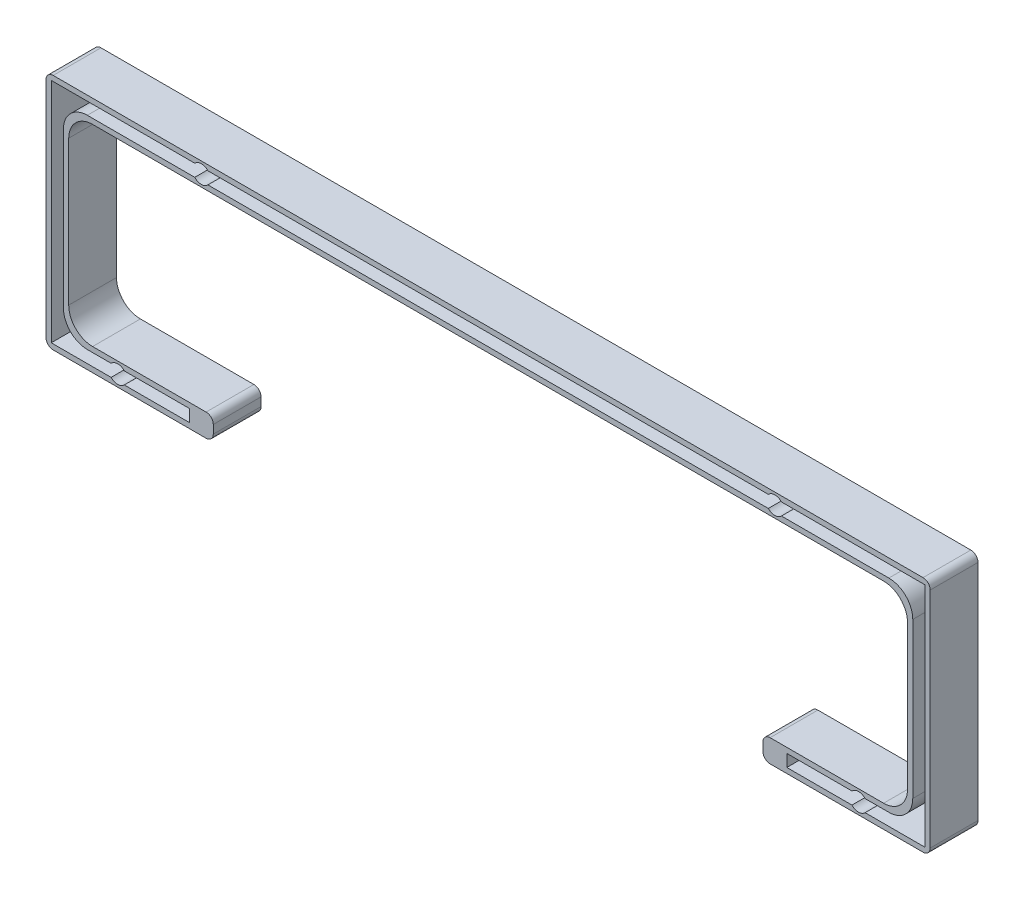
SolidWorks part; units mm, degrees
ref_plane "Front Plane" through (0, 0, 0) normal (0, 0, 1) x (1, 0, 0)
ref_plane "Top Plane" through (0, 0, 0) normal (0, 1, 0) x (1, 0, 0)
ref_plane "Right Plane" through (0, 0, 0) normal (1, 0, 0) x (0, 0, -1)
sketch "Sketch1" plane through (0, 0, 0) normal (0, 0, 1) x (1, 0, 0)
  line L0 (-115, 0) -> (-175.5, 0)
  line L1 (-175.5, 0) -> (-175.5, 80.5)
  line L2 (-175.5, 80.5) -> (175.5, 80.5)
  line L3 (0, 0) -> (0, 55.9082) construction
  line L4 (115, 0) -> (175.5, 0)
  line L5 (175.5, 0) -> (175.5, 80.5)
  line L6 (-115, -9.5) -> (-185, -9.5)
  line L7 (-185, -9.5) -> (-185, 90)
  line L8 (-185, 90) -> (185, 90)
  line L9 (185, -9.5) -> (185, 90)
  line L10 (115, -9.5) -> (185, -9.5)
  line L11 (-115, -9.5) -> (-115, 0)
  line L12 (115, -9.5) -> (115, 0)
  point P10 (0, 80.5)
  dimension "D1" = 9.5
  dimension "D2" = 90
  dimension "D3" = 70
  dimension "D4" = 370
extrude "Boss-Extrude1" add sketch "Sketch1" along normal blind 20
sketch "Sketch2" plane through (0, 0, 20) normal (0, 0, 1) x (1, 0, 0)
  line L1 (-125, -4.75) -> (-180.25, -4.75)
  line L2 (-180.25, -4.75) -> (-180.25, 85.25)
  line L3 (-180.25, 85.25) -> (180.25, 85.25)
  line L4 (180.25, 85.25) -> (180.25, -4.75)
  line L5 (180.25, -4.75) -> (125, -4.75)
  line L8 (-185, 90) -> (-185, -9.5) construction
  line L9 (-175.5, 0) -> (-175.5, 80.5) construction
  line L10 (-115, 0) -> (-175.5, 0) construction
  line L11 (185, 90) -> (-185, 90) construction
  line L12 (185, -9.5) -> (185, 90) construction
  line L13 (115, -9.5) -> (185, -9.5) construction
  line L14 (-115, -9.5) -> (-115, 0) construction
  line L15 (115, 0) -> (115, -9.5) construction
  dimension "D1" = 9.5
  dimension "D2" = 4.75
  dimension "D3" = 4.75
  dimension "D4" = 4.75
  dimension "D5" = 4.75
  dimension "D6" = 4.75
  dimension "D7" = 10
  dimension "D8" = 10
extrude "Cut-Extrude-Thin1" cut sketch "Sketch2" against normal offset from surface (17 mm away) 3 thin up to face at (0, 25.25, 0) thin type mid plane wall 5.1
fillet "Fillet1" radius 10 8 edges at (-175.5, 80.5, 10) (-175.5, 0, 10) (175.5, 0, 10) (175.5, 80.5, 10) (177.7, -2.2, 11.5) (177.7, 82.7, 11.5) (-177.7, -2.2, 11.5) (-177.7, 82.7, 11.5)
sketch "Sketch3" plane through (0, 0, 20) normal (0, 0, 1) x (1, 0, 0)
  line L0 (0, 0) -> (0, 23.1541) construction
  line L1 (185, 90) -> (-185, 90) construction
  line L2 (-165.5, 80.5) -> (165.5, 80.5) construction
  line L3 (-115, 0) -> (-165.5, 0) construction
  circle A0 centre (-120, 85.25) radius 3.75
  circle A1 centre (-120, 85.25) radius 2.25
  circle A2 centre (120, 85.25) radius 3.75
  circle A3 centre (120, 85.25) radius 2.25
  circle A4 centre (-155, -4.75) radius 3.75
  circle A5 centre (-155, -4.75) radius 2.25
  circle A6 centre (155, -4.75) radius 3.75
  circle A7 centre (155, -4.75) radius 2.25
  point P19 (0, 0)
  point P22 (-157.054, -4.75)
  dimension "D5" = 4.75
  dimension "D6" = 4.75
  dimension "D1" = 7.5
  dimension "D2" = 4.5
  dimension "D3" = 120
  dimension "D4" = 9.5
  dimension "D7" = 155
extrude "Cut-Extrude1" cut sketch "Sketch3" against normal up to surface (17 mm away) up to face at (0, 29, 3)
extrude "Cut-Extrude2" cut sketch "Sketch3<2>" against normal through all contours A1 | A5 | A7 | A3 region at (-120, 85.25, 20) region at (120, 85.25, 20) region at (-155, -4.75, 20) region at (155, -4.75, 20)
sketch "Sketch3<2>" plane through (0, 0, 20) normal (0, 0, 1) x (1, 0, 0) same geometry as "Sketch3"
fillet "Fillet2" radius 3 8 edges at (-115, -9.5, 10) (185, 90, 10) (115, -9.5, 10) (115, 0, 10) (-115, 0, 10) (185, -9.5, 10) (-185, -9.5, 10) (-185, 90, 10)
sketch "Sketch4" plane through (0, 0, 3) normal (0, 0, 1) x (1, 0, 0)
  line L0 (-152.2505, -2.2) -> (-125, -2.2) construction
  line L1 (-130, -2.2) -> (-125, -2.2)
  line L2 (-130, -2.2) -> (-130, -7.3)
  line L3 (-130, -7.3) -> (-125, -7.3)
  line L4 (-125, -2.2) -> (-125, -7.3)
  line L5 (-125, -7.3) -> (-152.2505, -7.3) construction
  line L6 (-125, -7.3) -> (-125, -2.2) construction
  line L7 (0, 0) -> (0, 19.514) construction
  line L8 (125, -2.2) -> (125, -7.3)
  line L9 (130, -7.3) -> (125, -7.3)
  line L10 (130, -2.2) -> (130, -7.3)
  line L11 (130, -2.2) -> (125, -2.2)
  dimension "D1" = 5
extrude "Cut-Extrude3" cut sketch "Sketch4" against normal through all
equation "\"D2@Sketch2\"=\"D1@Sketch2\"/2"
equation "\"D3@Sketch2\"=\"D1@Sketch2\"/2"
equation "\"D4@Sketch2\"=\"D1@Sketch2\"/2"
equation "\"D5@Sketch2\"=\"D2@Sketch2\""
equation "\"D6@Sketch2\"=\"D2@Sketch2\""
equation "\"D5@Sketch3\"=\"D4@Sketch3\"/2"
equation "\"D6@Sketch3\"=\"D5@Sketch3\""
